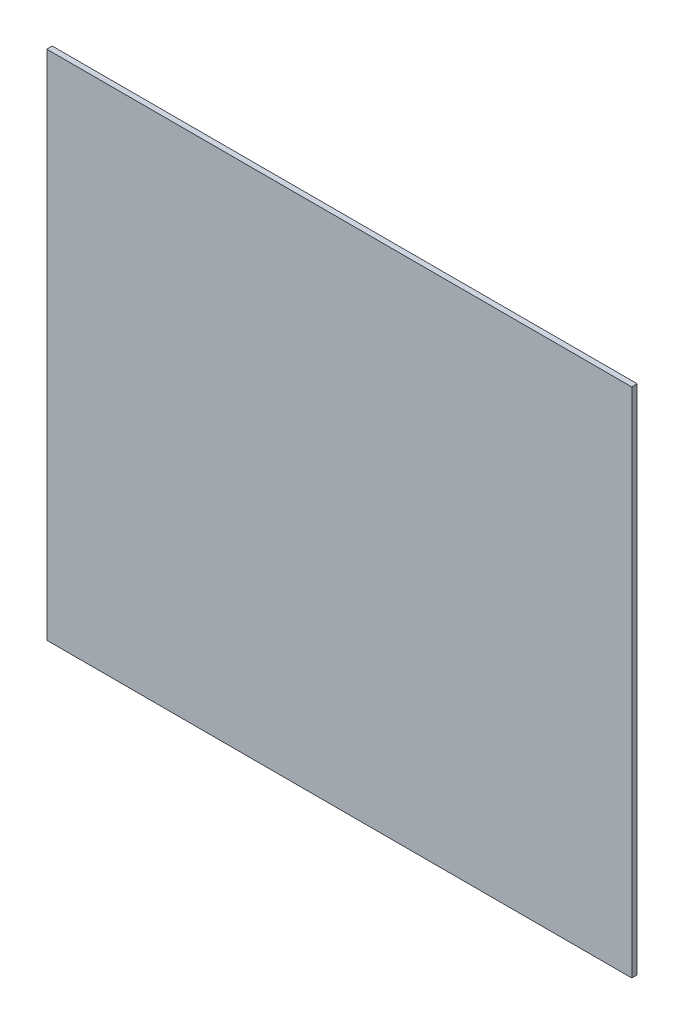
SolidWorks part; units mm, degrees
ref_plane "Front Plane" through (0, 0, 0) normal (0, 0, 1) x (1, 0, 0)
ref_plane "Top Plane" through (0, 0, 0) normal (0, 1, 0) x (1, 0, 0)
ref_plane "Right Plane" through (0, 0, 0) normal (1, 0, 0) x (0, 0, -1)
sketch "Sketch1" plane through (0, 0, 0) normal (0, 0, 1) x (1, 0, 0)
  line L1 (-160, -140) -> (160, -140)
  line L2 (-160, -140) -> (-160, 140)
  line L3 (-160, 140) -> (160, 140)
  line L4 (160, -140) -> (160, 140)
  line L5 (-160, -140) -> (160, 140) construction
  line L6 (-160, 140) -> (160, -140) construction
  point P0 (0, 0)
  dimension "D1" = 320
  dimension "D2" = 280
extrude "Boss-Extrude1" add sketch "Sketch1" along normal blind 3
equation "\"PCLength\"= 320mm'Length across I/O from PS to GPU"
equation "\"PCWidth\"= 242mm'Distance of longest part parallel to GPU(ussually GPU)"
equation "\"PCHeight\"= 172mm'Tallest point with mobo laying flat"
equation "\"WallThickness\"= 9mm'Thickness of each outer tank wall"
equation "\"ThermoBarrierThickness\"= 3mm'Thickness of barrier between hot side and cold side"
equation "\"HotSideGap\"= 35mm'Space in the hot side for a pump"
equation "\"PCClearance\"= 30mm'Clearance from top of tank to top of PC"
equation "\"RadiatorHeight\"= 275mm'Final Height from ground of radiators"
equation "\"D1@Sketch1\"=\"PCLength\""
equation "\"D2@Sketch1\"=\"RadiatorHeight\" + 5"
equation "\"D1@Boss-Extrude1\"=\"ThermoBarrierThickness\""
